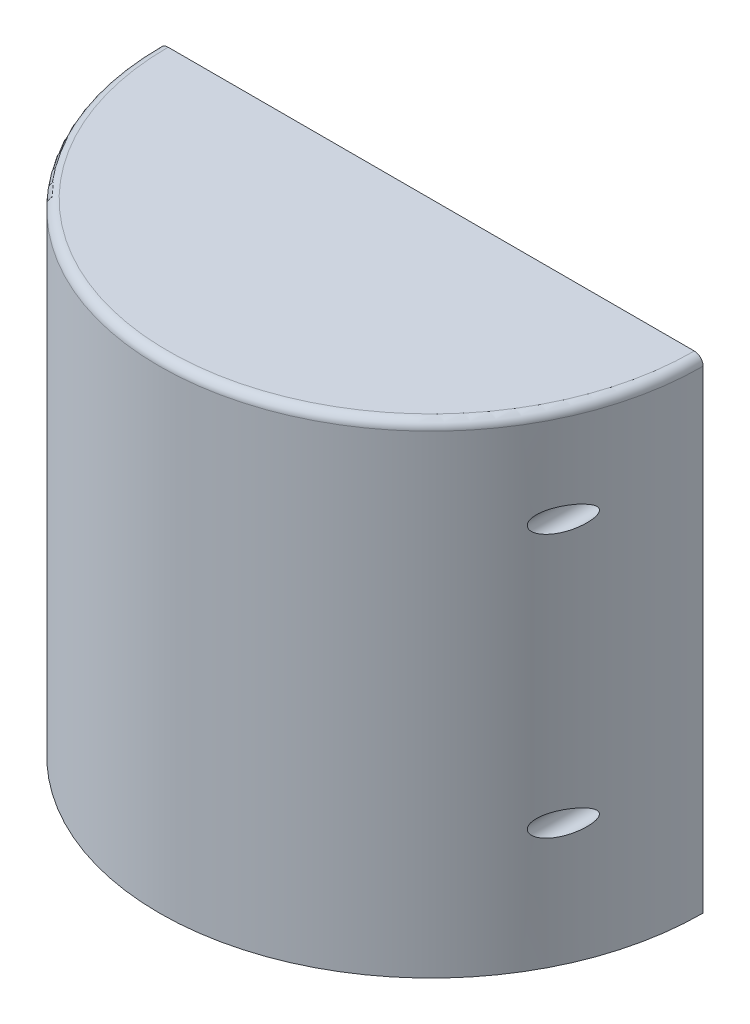
SolidWorks part; units mm, degrees
material "ABS"
ref_plane "Спереди" through (0, 0, 0) normal (0, 0, 1) x (1, 0, 0)
ref_plane "Сверху" through (0, 0, 0) normal (0, 1, 0) x (1, 0, 0)
ref_plane "Справа" through (0, 0, 0) normal (1, 0, 0) x (0, 0, -1)
sketch "Эскиз1" plane through (0, 0, 0) normal (0, 1, 0) x (1, 0, 0)
  line L0 (-31, 0) -> (-28, 0)
  line L1 (28, 0) -> (31, 0)
  arc A2 (31, 0) -> (-31, 0) centre (0, 0) cw
  arc A3 (28, 0) -> (-28, 0) centre (0, 0) cw
  dimension "D1" = 28
  dimension "D2" = 31
extrude "Бобышка-Вытянуть1" add sketch "Эскиз1" along normal blind 55
sketch "Эскиз2" plane through (0, 55, 0) normal (0, 1, 0) x (1, 0, 0)
  line L0 (-31, 0) -> (31, 0)
  arc A3 (31, 0) -> (-31, 0) centre (0, 0) cw
  arc A4 (-31, 0) -> (31, 0) centre (0, 0) ccw construction
sketch "Эскиз12" plane through (0, 0, 0) normal (0, 0, -1) x (-1, 0, 0)
  line L0 (28, 55) -> (28, 0) construction
  line L2 (28, 14) -> (28, 44) construction
  line L4 (28, 14) -> (28, 44) construction
  line L5 (28, 55) -> (28, 0) construction
  line L6 (0, 59.3805) -> (0, 0) construction
  line L7 (-28, 0) -> (28, 0) construction
  line L8 (28, 55) -> (28, 0) construction
  circle A1 centre (28, 44) radius 3
  circle A3 centre (28, 14) radius 3
  circle A4 centre (-28, 44) radius 3
  circle A5 centre (-28, 14) radius 3
  point P8 (28, 29)
  dimension "D3" = 6
  dimension "D1" = 30
  dimension "D2" = 29
extrude "Бобышка-Вытянуть5" add sketch "Эскиз12" against normal up to surface (12.6095 mm away) up to face at (0, 27.5, 14)
sketch "Эскиз16" plane through (0, 0, 0) normal (0, 0, -1) x (-1, 0, 0)
  line L0 (0, 60.4355) -> (0, 0) construction
  circle A1 centre (28, 44) radius 1.3
  circle A3 centre (28, 14) radius 1.3
  circle A4 centre (-28, 14) radius 1.3
  circle A5 centre (-28, 44) radius 1.3
  dimension "D1" = 2.6
extrude "Вырез-Вытянуть2" cut sketch "Эскиз16" against normal through all
extrude "Бобышка-Вытянуть6" add sketch "Эскиз2" against normal blind 3
fillet "Скругление1" radius 1 1 edges at (0, 55, 31)
